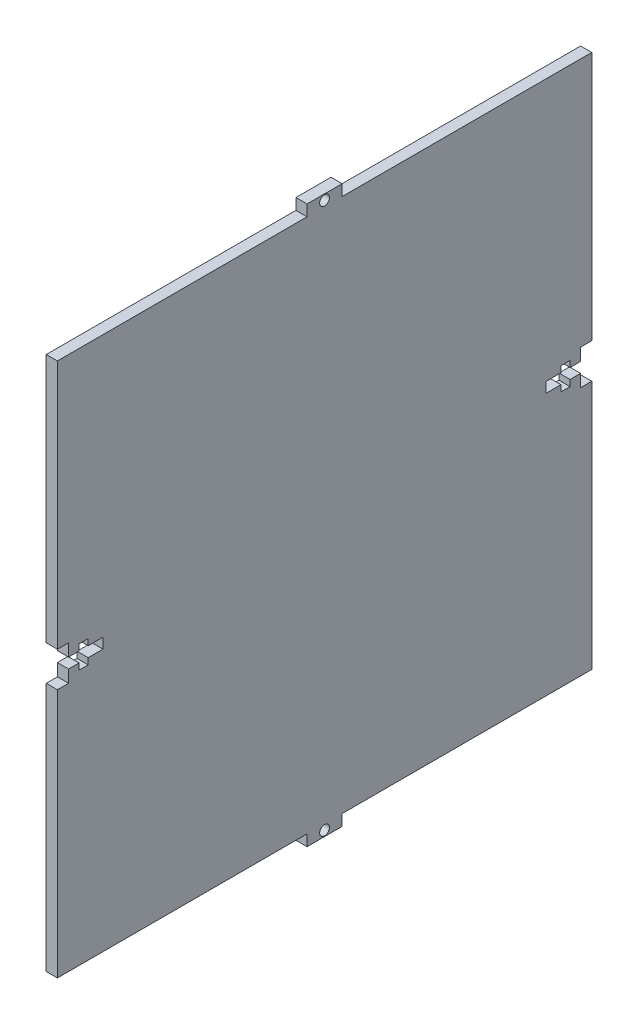
SolidWorks part; units mm, degrees
ref_plane "Front Plane" through (0, 0, 0) normal (0, 0, 1) x (1, 0, 0)
ref_plane "Top Plane" through (0, 0, 0) normal (0, 1, 0) x (1, 0, 0)
ref_plane "Right Plane" through (0, 0, 0) normal (1, 0, 0) x (0, 0, -1)
sketch "Sketch1" plane through (0, 0, 0) normal (1, 0, 0) x (0, 0, -1)
  line L1 (76.2, 76.2) -> (-76.2, 76.2)
  line L2 (76.2, 76.2) -> (76.2, -76.2)
  line L3 (76.2, -76.2) -> (-76.2, -76.2)
  line L4 (-76.2, 76.2) -> (-76.2, -76.2)
  line L5 (76.2, 76.2) -> (-76.2, -76.2) construction
  line L6 (76.2, -76.2) -> (-76.2, 76.2) construction
  point P0 (0, 0)
  dimension "D1" = 152.4
  dimension "D2" = 152.4
extrude "Boss-Extrude1" add sketch "Sketch1" along normal blind 3.18
sketch "Sketch3" plane through (0, 0, 0) normal (-1, 0, 0) x (0, 0, 1)
  line L1 (0, 0) -> (-76.2, 0) construction
  line L2 (-76.2, -76.2) -> (-76.2, 76.2) construction
  line L3 (0, -76.2) -> (0, 76.2) construction
  line L9 (0, 0) -> (76.2, 0) construction
  line L10 (76.2, -76.2) -> (-76.2, -76.2) construction
  line L12 (76.2, 76.2) -> (76.2, -76.2) construction
  line L13 (-76.2, 76.2) -> (76.2, 76.2) construction
  line L14 (5, -76.2) -> (-5, -76.2)
  line L15 (5, -79.38) -> (-5, -79.38)
  line L16 (5, -79.38) -> (5, -76.2)
  line L18 (-5, -79.38) -> (-5, -76.2)
  line L22 (0, -79.38) -> (0, -70.042) construction
  line L23 (5, -77.79) -> (-5, -77.79) construction
  line L27 (5, 76.2) -> (5, 79.38)
  line L28 (5, 79.38) -> (-5, 79.38)
  line L29 (-5, 76.2) -> (-5, 79.38)
  line L30 (5, 77.79) -> (-5, 77.79) construction
  line L31 (0, 76.2) -> (0, 79.38) construction
  line L32 (5, 76.2) -> (-5, 76.2)
  line L33 (0, 57.9987) -> (0, 76.2)
  circle A0 centre (0, -77.79) radius 1.4
  circle A1 centre (0, 77.79) radius 1.4
  point P31 (0, 67.0994)
  line M14 (76.2, 76.2) -> (-76.2, 76.2)
  line M16 (-76.2, -76.2) -> (76.2, -76.2)
  dimension "D5" = 2.8
  dimension "D6" = 2.8
  dimension "D2" = 10
  dimension "D3" = 3.18
  dimension "D4" = 10
  dimension "D1" = 3.18
extrude "Boss-Extrude5" add sketch "Sketch3" against normal blind 3.18 contours L29 L32 L27 L28 A1 M14 | L18 L15 L16 A0 M16 region at (0, -77.79, 4.8951) region at (0, 76.3049, 2.5)
sketch "Sketch4" plane through (0, 0, 0) normal (1, 0, 0) x (0, 0, -1)
  line L2 (0, 0) -> (-76.2, 0) construction
  line L3 (-76.2, 76.2) -> (-76.2, -76.2) construction
  line L4 (-76.2, -5) -> (-76.2, 5)
  line L5 (-76.2, -5) -> (-73.02, -5)
  line L7 (-76.2, 5) -> (-73.02, 5)
  line L8 (-73.02, -5) -> (-73.02, -1.47)
  line L9 (-73.02, 1.47) -> (-73.02, 5)
  line L10 (-73.02, -1.47) -> (-70.02, -1.47)
  line L12 (-73.02, 1.47) -> (-70.02, 1.47)
  line L13 (-63.2, -1.47) -> (-63.2, 1.47)
  line L14 (-67.42, -1.47) -> (-63.2, -1.47)
  line L15 (-70.02, -3.25) -> (-67.42, -3.25)
  line L16 (-70.02, -3.25) -> (-70.02, -1.47)
  line L17 (-70.02, 3.25) -> (-67.42, 3.25)
  line L18 (-67.42, -3.25) -> (-67.42, -1.47)
  line L19 (-67.42, 1.47) -> (-63.2, 1.47)
  line L20 (-70.02, 1.47) -> (-70.02, 3.25)
  line L21 (-67.42, 1.47) -> (-67.42, 3.25)
  dimension "D1" = 3.18
  dimension "D2" = 10
  dimension "D3" = 2.94
  dimension "D4" = 6.5
  dimension "D5" = 2.6
  dimension "D6" = 13
  dimension "D7" = 3
extrude "Cut-Extrude2" cut sketch "Sketch4" along normal through all contours L18 L14 L13 L19 L21 L17 L20 L12 L9 L7 L4 L5 L8 L10 L16 L15
sketch "Sketch5" plane through (0, 0, 0) normal (-1, 0, 0) x (0, 0, 1)
  line L0 (0, 0) -> (-76.2, 0) construction
  line L1 (-76.2, -76.2) -> (-76.2, 76.2) construction
  line L2 (-70.02, -1.47) -> (-73.02, -1.47)
  line L3 (-76.2, -5) -> (-73.02, -5)
  line L4 (-76.2, -5) -> (-76.2, 5)
  line L5 (-76.2, 5) -> (-73.02, 5)
  line L6 (-73.02, -5) -> (-73.02, -1.47)
  line L7 (-63.2, -1.47) -> (-67.42, -1.47)
  line L8 (-63.2, -1.47) -> (-63.2, 1.47)
  line L9 (-63.2, 1.47) -> (-67.42, 1.47)
  line L13 (-67.42, 3.25) -> (-70.02, 3.25)
  line L14 (-67.42, 3.25) -> (-67.42, 1.47)
  line L15 (-67.42, -3.25) -> (-70.02, -3.25)
  line L16 (-70.02, 3.25) -> (-70.02, 1.47)
  line L17 (-70.02, -1.47) -> (-70.02, -3.25)
  line L20 (-67.42, -1.47) -> (-67.42, -3.25)
  line L22 (-70.02, 1.47) -> (-73.02, 1.47)
  line L23 (-73.02, 1.47) -> (-73.02, 5)
  point P9 (-39.8999, 0)
  dimension "D1" = 10
  dimension "D2" = 3.18
  dimension "D3" = 3
  dimension "D4" = 2.6
  dimension "D5" = 2.6
  dimension "D6" = 2.94
  dimension "D7" = 13
  dimension "D8" = 6.5
  dimension "D9" = 6.5
  dimension "D10" = 4.22
extrude "Cut-Extrude3" cut sketch "Sketch5" against normal through all
equation "\"sheet\"= 3.18mm"
equation "\"tabW\"= 15mm"
equation "\"4-40Diam\" = 2.94mm"
equation "\"nutDiam\" = 6.5mm"
equation "\"nutThickness\"= 2.6mm"
